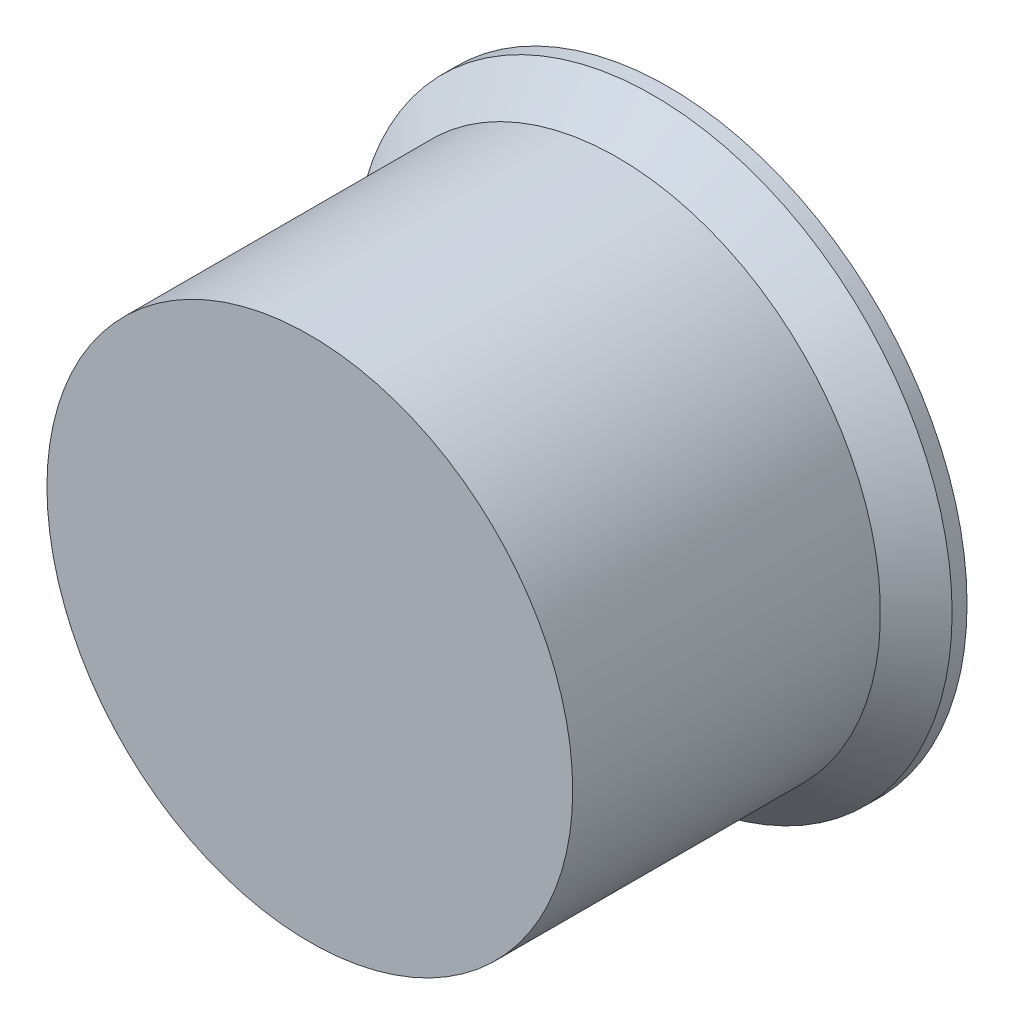
SolidWorks part; units mm, degrees
ref_plane "Front Plane" through (0, 0, 0) normal (0, 0, 1) x (1, 0, 0)
ref_plane "Top Plane" through (0, 0, 0) normal (0, 1, 0) x (1, 0, 0)
ref_plane "Right Plane" through (0, 0, 0) normal (1, 0, 0) x (0, 0, -1)
sketch "Sketch1" plane through (0, 0, 0) normal (0, 0, 1) x (1, 0, 0)
  circle A0 centre (0, 0) radius 5
  dimension "D1" = 10
extrude "Boss-Extrude1" add sketch "Sketch1" along normal blind 1
sketch "Sketch2" plane through (0, 0, 1) normal (0, 0, 1) x (1, 0, 0)
  circle A0 centre (0, 0) radius 4.4
  dimension "D1" = 8.8
extrude "Boss-Extrude2" add sketch "Sketch2" along normal blind 5
chamfer "Chamfer1" distance 0.75 angle 45 1 edges at (5, 0, 1)
